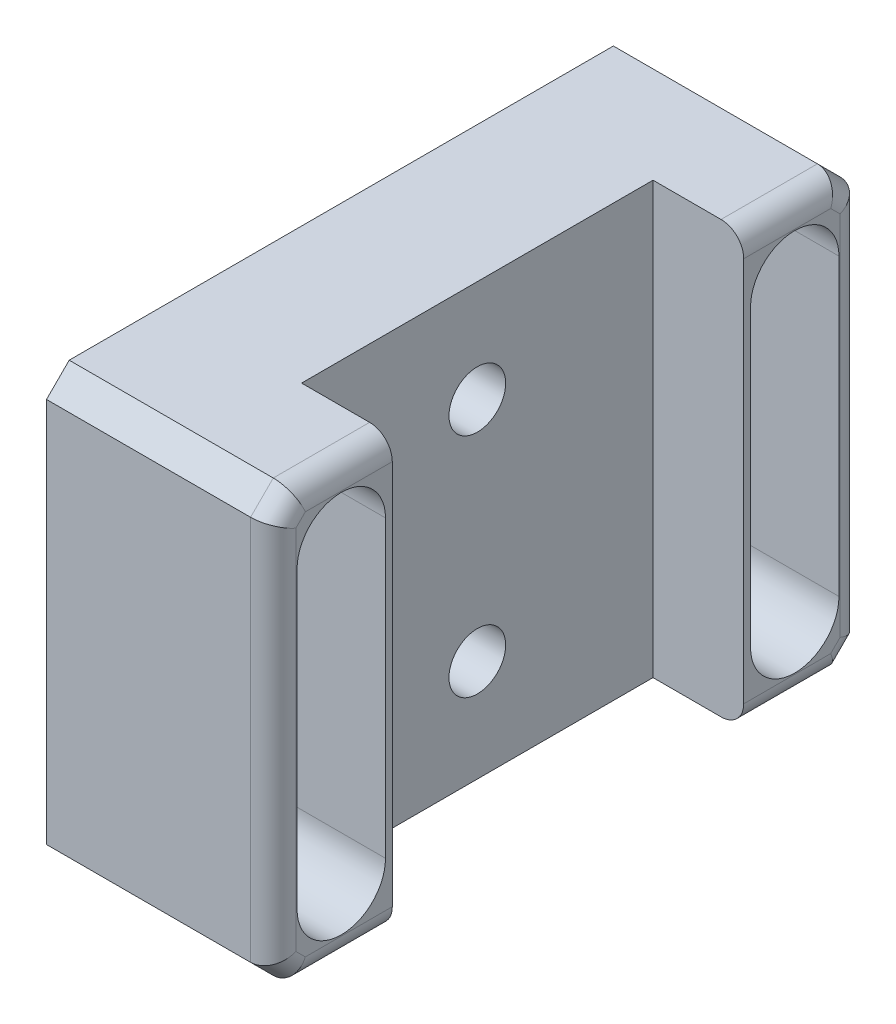
SolidWorks part; units mm, degrees
ref_plane "Спереди" through (0, 0, 0) normal (0, 0, 1) x (1, 0, 0)
ref_plane "Сверху" through (0, 0, 0) normal (0, 1, 0) x (1, 0, 0)
ref_plane "Справа" through (0, 0, 0) normal (1, 0, 0) x (0, 0, -1)
sketch "Эскиз1" plane through (0, 0, 0) normal (1, 0, 0) x (0, 0, -1)
  line L0 (-10, 6.5) -> (-10, -6.5) construction
  line L1 (-13, 9.5) -> (13, 9.5)
  line L2 (-13, 9.5) -> (-13, -9.5)
  line L3 (-13, -9.5) -> (13, -9.5)
  line L4 (13, 9.5) -> (13, -9.5)
  line L5 (-13, 9.5) -> (13, -9.5) construction
  line L6 (-13, -9.5) -> (13, 9.5) construction
  line L7 (-8.75, 6.5) -> (-8.75, -6.5)
  line L8 (-11.25, 6.5) -> (-11.25, -6.5)
  line L9 (0, 9.5) -> (0, -9.5) construction
  line L10 (10, 6.5) -> (10, -6.5) construction
  line L11 (8.75, 6.5) -> (8.75, -6.5)
  line L12 (11.25, 6.5) -> (11.25, -6.5)
  arc A0 (-8.75, 6.5) -> (-11.25, 6.5) centre (-10, 6.5) ccw
  arc A1 (-11.25, -6.5) -> (-8.75, -6.5) centre (-10, -6.5) ccw
  arc A2 (8.75, 6.5) -> (11.25, 6.5) centre (10, 6.5) cw
  arc A3 (11.25, -6.5) -> (8.75, -6.5) centre (10, -6.5) cw
  point P0 (0, 0)
  point P8 (-10, 0)
  point P17 (10, 0)
  dimension "D1" = 26
  dimension "D2" = 2.5
  dimension "D3" = 20
  dimension "D5" = 3
  dimension "D4" = 19
extrude "Бобышка-Вытянуть1" add sketch "Эскиз1" along normal blind 10
sketch "Эскиз2" plane through (10, 0, 0) normal (1, 0, 0) x (0, 0, -1)
  line L0 (-13, -9.5) -> (13, -9.5) construction
  line L1 (7.75, 9.5) -> (-7.75, 9.5)
  line L2 (7.75, 9.5) -> (7.75, -9.5)
  line L3 (7.75, -9.5) -> (-7.75, -9.5)
  line L4 (-7.75, 9.5) -> (-7.75, -9.5)
  line L5 (7.75, 9.5) -> (-7.75, -9.5) construction
  line L6 (7.75, -9.5) -> (-7.75, 9.5) construction
  point P0 (0, 0)
  dimension "D1" = 15.5
extrude "Вырез-Вытянуть1" cut sketch "Эскиз2" against normal blind 4
sketch "Эскиз3" plane through (10, 0, 0) normal (1, 0, 0) x (0, 0, -1)
  line L0 (-10, -6.5) -> (-10, 6.5) construction
  line L1 (-11.95, -6.5) -> (-11.95, 6.5)
  line L2 (-8.05, -6.5) -> (-8.05, 6.5)
  line L3 (0, 9.5) -> (0, -9.5) construction
  line L4 (7.75, 9.5) -> (-7.75, 9.5) construction
  line L5 (-7.75, -9.5) -> (7.75, -9.5) construction
  line L6 (10, -6.5) -> (10, 6.5) construction
  line L7 (11.95, -6.5) -> (11.95, 6.5)
  line L8 (8.05, -6.5) -> (8.05, 6.5)
  arc A0 (-11.95, -6.5) -> (-8.05, -6.5) centre (-10, -6.5) ccw
  arc A1 (-8.05, 6.5) -> (-11.95, 6.5) centre (-10, 6.5) ccw
  arc A2 (-11.25, -6.5) -> (-8.75, -6.5) centre (-10, -6.5) ccw construction
  arc A3 (-8.75, 6.5) -> (-11.25, 6.5) centre (-10, 6.5) ccw construction
  arc A4 (11.95, -6.5) -> (8.05, -6.5) centre (10, -6.5) cw
  arc A5 (8.05, 6.5) -> (11.95, 6.5) centre (10, 6.5) cw
  point P2 (-10, 0)
  point P23 (10, 0)
  dimension "D1" = 3.9
extrude "Вырез-Вытянуть2" cut sketch "Эскиз3" against normal blind 4
chamfer "Фаска1" distance 1 angle 45 4 edges at (5, 9.5, -13) (5, -9.5, -13) (5, -9.5, 13) (5, 9.5, 13)
fillet "Скругление1" radius 1 10 edges at (10, 9, 12.5) (10, -9, 12.5) (10, -9, -12.5) (10, -9.5, -9.875) (10, 0, -13) (10, 9, -12.5) (10, 9.5, -9.875) (10, -9.5, 9.875) (10, 9.5, 9.875) (10, 0, 13)
sketch "Эскиз4" plane through (6, 0, 0) normal (1, 0, 0) x (0, 0, -1)
  line L0 (0, 9.5) -> (0, -9.5) construction
  line L1 (7.75, 9.5) -> (-7.75, 9.5) construction
  line L2 (-7.75, -9.5) -> (7.75, -9.5) construction
  line L3 (-7.75, 0) -> (7.75, 0) construction
  line L4 (-7.75, 9.5) -> (-7.75, -9.5) construction
  line L5 (7.75, -9.5) -> (7.75, 9.5) construction
  circle A0 centre (0, 5) radius 1.25
  circle A1 centre (0, -5) radius 1.25
  dimension "D1" = 2.5
  dimension "D2" = 10
extrude "Вырез-Вытянуть3" cut sketch "Эскиз4" against normal through all
sketch "Эскиз5" plane through (0, 0, 0) normal (-1, 0, 0) x (0, 0, 1)
  line L1 (1.1691, 2.975) -> (2.3383, 5)
  line L2 (2.3383, 5) -> (1.1691, 7.025)
  line L3 (1.1691, 7.025) -> (-1.1691, 7.025)
  line L4 (-1.1691, 7.025) -> (-2.3383, 5)
  line L5 (-2.3383, 5) -> (-1.1691, 2.975)
  line L6 (-1.1691, 2.975) -> (1.1691, 2.975)
  line L7 (1.1691, -7.025) -> (2.3383, -5)
  line L8 (2.3383, -5) -> (1.1691, -2.975)
  line L9 (1.1691, -2.975) -> (-1.1691, -2.975)
  line L10 (-1.1691, -2.975) -> (-2.3383, -5)
  line L11 (-2.3383, -5) -> (-1.1691, -7.025)
  line L12 (-1.1691, -7.025) -> (1.1691, -7.025)
  circle A0 centre (0, 5) radius 2.025 construction
  circle A1 centre (0, -5) radius 2.025 construction
  dimension "D1" = 4.05
  dimension "D2" = 4.05
extrude "Вырез-Вытянуть4" cut sketch "Эскиз5" against normal blind 3
equation "\"motor_diameter\"= 30"
equation "\"mm_diameter\"= IIF ( \"motor_diameter\" < 34 , 41 , \"motor_diameter\" + 8 )"
equation "\"upper_shafts_diameter\"= 5"
equation "\"upper_shats_length\"= 180"
equation "\"upper_bearing_d1\"= 10"
equation "\"upper_bearing_d2\"= 5"
equation "\"upper_bearing_h\"= 15"
equation "\"lower_shafts_diameter\"= 5"
equation "\"lower_shafts_length\"= 180"
equation "\"lower_bearing_d1\"= 10"
equation "\"lower_bearing_d2\"= 5"
equation "\"lower_bearing_h\"= 15"
equation "\"print_offset\"= 0.5"
equation "\"bh_screws_d\"= 2"
equation "\"bh_screws_h\"= 20"
equation "\"bh_screws_hh_d\"= 3.4"
equation "\"bh_screws_hh_h\"= 2"
equation "\"bh_nut_d\"= 3.8"
equation "\"bh_nut_h\"= 2"
equation "\"motor_screws_d\"= 3"
equation "\"motor_screws_h\"= 16"
equation "\"motor_screws_hh_d\"= 5.5"
equation "\"motor_screws_hh_h\"= 3"
equation "\"plate_hole_distance\"= 25.4"
equation "\"plate_screws_d\"= 6.5"
equation "\"shafts_diameter\"= IIF ( \"mm_diameter\" < 42 , 42 + 8 , \"mm_diameter\" + 8 )"
equation "\"central_hole_diameter\"= 8"
equation "\"bh_thikness\"= 4"
equation "\"ends_screws_d\"= 4"
equation "\"ends_screws_h\"= 16"
equation "\"ends_screws_hh_d\"= 6.7"
equation "\"ends_screws_hh_h\"= 4.1"
equation "\"ends_nut_d\"= 6.8"
equation "\"ends_nut_h\"= 3"
equation "\"system_radius\" = ( \"shafts_diameter\" + 12 + \"bh_thikness\" / 2 ) / 2"
equation "\"encoder_distance\"= \"system_radius\" + 4"
equation "\"tape_position\"= \"encoder_distance\" - 2 + 3.9 + 1.7 / 2"
equation "\"D2@Эскиз1\"=\"bh_screws_d\"+\"print_offset\""
equation "\"D1@Бобышка-Вытянуть1\"=6"
equation "\"D4@Эскиз1\"=\"upper_bearing_h\" + 6 + 3 - 8 + 3"
equation "\"D1@Эскиз2\"=\"print_offset\"+15"
equation "\"D1@Эскиз3\"=\"bh_screws_hh_d\"+\"print_offset\""
equation "\"D1@Вырез-Вытянуть2\"=\"bh_screws_hh_h\"+2"
equation "\"D1@Эскиз4\"=\"bh_screws_d\"+\"print_offset\""
equation "\"D1@Эскиз5\"=\"bh_nut_d\"+\"print_offset\"/2"
equation "\"D2@Эскиз5\"=\"D1@Эскиз5\""
equation "\"D1@Вырез-Вытянуть4\"=\"bh_nut_h\"+1"
equation "\"ft_sensor_d1\" = 9.8"
equation "\"ft_sensor_d2\"= 24.9"
equation "\"ft_sensor_h\"= 7"
equation "\"carbon_pipe_d\"= 14"
